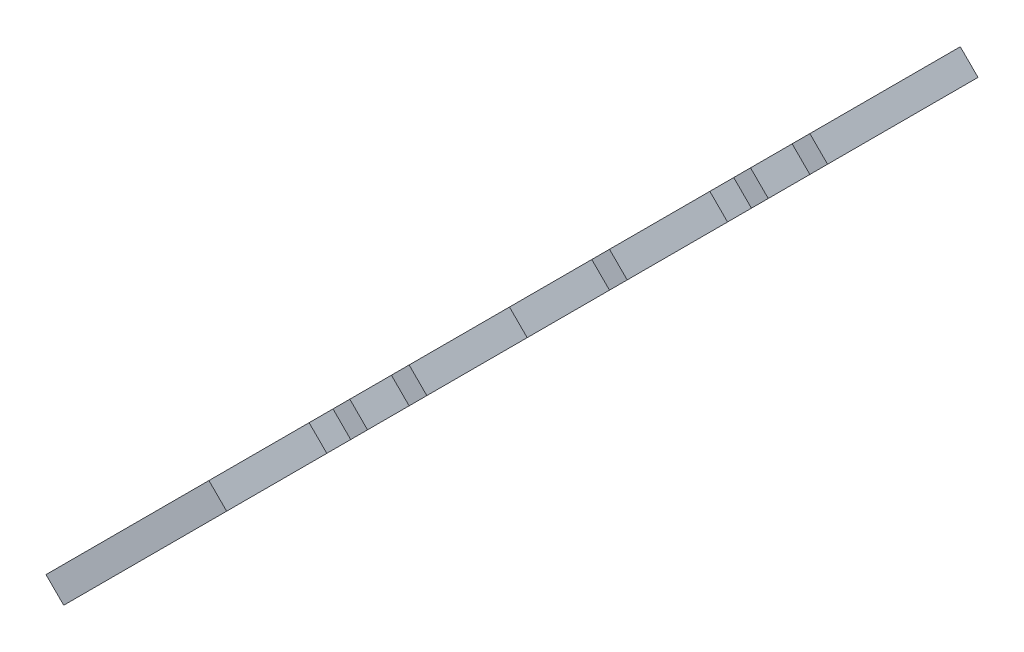
SolidWorks part; units mm, degrees
ref_plane "Front Plane" through (0, 0, 0) normal (0, 0, 1) x (1, 0, 0)
ref_plane "Top Plane" through (0, 0, 0) normal (0, 1, 0) x (1, 0, 0)
ref_plane "Right Plane" through (0, 0, 0) normal (1, 0, 0) x (0, 0, -1)
sketch "Sketch1" plane through (0, 0, 0) normal (0, 0, 1) x (1, 0, 0)
  line L0 (-110.4572, 6.7859) -> (-69.148, 48.095)
  line L1 (-110.4572, 6.7859) -> (-114.9473, 11.276)
  line L2 (-69.148, 48.095) -> (-73.6381, 52.5852)
  line L3 (-114.9473, 11.276) -> (-73.6381, 52.5852)
  line L4 (-74.5361, -29.1352) -> (-70.046, -24.645) construction
extrude "Boss-Extrude1" add sketch "Sketch1" along normal up to surface (190.5 mm away)
sketch "Sketch2" plane through (-63.1116, 63.1116, 0) normal (-0.7071, 0.7071, 0) x (0, 0, 1)
  line L0 (190.5, -14.8867) -> (0, -14.8867) construction
  line L1 (165.1, -21.2367) -> (139.7412, -21.2367)
  line L2 (165.1, -21.2367) -> (165.1, -14.8867)
  line L3 (165.1, -14.8867) -> (139.7412, -14.8867)
  line L4 (139.7412, -21.2367) -> (139.7412, -14.8867)
  line L5 (190.5, -73.3067) -> (0, -73.3067) construction
  line L6 (165.1, -66.9567) -> (139.7412, -66.9567)
  line L7 (165.1, -66.9567) -> (165.1, -73.3067)
  line L8 (165.1, -73.3067) -> (139.7412, -73.3067)
  line L9 (139.7412, -66.9567) -> (139.7412, -73.3067)
  dimension "D1" = 25.3588
extrude "Cut-Extrude1" cut sketch "Sketch2" against normal blind 6.35
pattern_linear "LPattern1" count 3 spacing 50.8 along (0, 0, -1) of "Cut-Extrude1"
sketch "Sketch3" plane through (0, 0, 0) normal (0, 0, -1) x (-1, 0, 0)
  line L0 (94.2927, 22.9503) -> (98.7828, 27.4404)
  line L1 (110.4572, 6.7859) -> (69.148, 48.095) construction
  line L2 (73.6381, 52.5852) -> (114.9473, 11.276) construction
  line L3 (98.7828, 27.4404) -> (89.8026, 36.4207)
  line L4 (89.8026, 36.4207) -> (85.3124, 31.9306)
  line L6 (85.3124, 31.9306) -> (94.2927, 22.9503)
  line L7 (98.7828, 36.4207) -> (83.4753, 21.1131) construction
  line L8 (69.148, 48.095) -> (73.6381, 52.5852) construction
  line L9 (114.9473, 11.276) -> (110.4572, 6.7859) construction
  dimension "D1" = 12.7
  dimension "D2" = 6.35
extrude "Boss-Extrude2" add sketch "Sketch3" along normal blind 6.35
sketch "Sketch5" plane through (-58.6215, 58.6215, 0) normal (0.7071, -0.7071, 0) x (0, 0, -1)
  line L0 (-179.9336, -73.3067) -> (-175.6664, -66.9567) construction
  line L1 (-190.5, -73.3067) -> (-165.1, -73.3067) construction
  line L2 (-179.9336, -66.9567) -> (-179.9336, -73.3067) construction
  line L3 (-175.6664, -73.3067) -> (-179.9336, -66.9567) construction
  line L4 (-175.6664, -66.9567) -> (-175.6664, -73.3067) construction
  line L5 (-78.3336, -73.3067) -> (-74.0664, -66.9567) construction
  line L6 (-88.9412, -73.3067) -> (-63.5, -73.3067) construction
  line L7 (-78.3336, -66.9567) -> (-78.3336, -73.3067) construction
  line L8 (-74.0664, -73.3067) -> (-78.3336, -66.9567) construction
  line L9 (-74.0664, -66.9567) -> (-74.0664, -73.3067) construction
  line L10 (-18.0086, -73.3067) -> (-13.7414, -66.9567) construction
  line L11 (-38.1412, -73.3067) -> (0, -73.3067) construction
  line L12 (-18.0086, -66.9567) -> (-18.0086, -73.3067) construction
  line L13 (-13.7414, -73.3067) -> (-18.0086, -66.9567) construction
  line L14 (-13.7414, -66.9567) -> (-13.7414, -73.3067) construction
  circle A0 centre (-177.8, -70.1317) radius 2.0955
  circle A1 centre (-76.2, -70.1317) radius 2.0955
  circle A2 centre (-15.875, -70.1317) radius 2.0955
  dimension "D1" = 4.191
extrude "Cut-Extrude2" cut sketch "Sketch5" against normal through all
ref_plane "Midplane" through (-31.1811, -31.1811, 0) normal (-0.7071, -0.7071, 0) x (-0.7071, 0.7071, 0)
mirror "Mirror1" about plane through (-31.1811, -31.1811, 0) normal (-0.7071, -0.7071, 0) of "Cut-Extrude2"
sketch "Sketch6" plane through (-63.1116, 63.1116, 0) normal (-0.7071, 0.7071, 0) x (0, 0, 1)
  line L0 (152.4206, -3.6091) -> (152.4206, -40.9822) construction
  line L1 (139.7412, -14.8867) -> (139.7412, -21.2367) construction
  line L2 (165.1, -21.2367) -> (165.1, -14.8867) construction
  line L3 (50.8206, 6.6062) -> (50.8206, -35.0025) construction
  line L4 (38.1412, -14.8867) -> (38.1412, -21.2367) construction
  line L5 (63.5, -21.2367) -> (63.5, -14.8867) construction
  line L7 (38.1412, -21.2367) -> (63.5, -21.2367) construction
  line L11 (139.7412, -21.2367) -> (165.1, -21.2367) construction
  line B0 (52.9542, -21.2367) -> (48.687, -21.2367)
  line B1 (48.687, -33.1747) -> (46.3756, -33.1747)
  line B2 (46.3756, -33.1747) -> (46.3756, -29.9997)
  line B3 (46.3756, -29.9997) -> (48.687, -29.9997)
  line B4 (48.687, -29.9997) -> (48.687, -21.2367)
  line B5 (48.687, -33.1747) -> (48.687, -36.4767)
  line B6 (48.687, -36.4767) -> (52.9542, -36.4767)
  line B7 (52.9542, -33.1747) -> (52.9542, -36.4767)
  line B8 (52.9542, -29.9997) -> (52.9542, -21.2367)
  line B9 (55.2656, -29.9997) -> (52.9542, -29.9997)
  line B10 (55.2656, -33.1747) -> (55.2656, -29.9997)
  line B11 (52.9542, -33.1747) -> (55.2656, -33.1747)
  line B12 (154.5542, -21.2367) -> (150.287, -21.2367)
  line B13 (150.287, -33.1747) -> (147.9756, -33.1747)
  line B14 (147.9756, -33.1747) -> (147.9756, -29.9997)
  line B15 (147.9756, -29.9997) -> (150.287, -29.9997)
  line B16 (150.287, -29.9997) -> (150.287, -21.2367)
  line B17 (150.287, -33.1747) -> (150.287, -36.4767)
  line B18 (150.287, -36.4767) -> (154.5542, -36.4767)
  line B19 (154.5542, -33.1747) -> (154.5542, -36.4767)
  line B20 (154.5542, -29.9997) -> (154.5542, -21.2367)
  line B21 (156.8656, -29.9997) -> (154.5542, -29.9997)
  line B22 (156.8656, -33.1747) -> (156.8656, -29.9997)
  line B23 (154.5542, -33.1747) -> (156.8656, -33.1747)
sketch_block_instance "TSlot-1"
sketch_block "TSlot" parameters "D1"=3.302, "D2"=3.175
sketch_block_instance "TSlot-2"
extrude "Cut-Extrude3" cut sketch "Sketch6" against normal through all
mirror "Mirror2" about plane through (-31.1811, -31.1811, 0) normal (-0.7071, -0.7071, 0) of "Cut-Extrude3"
sketch "Sketch7" plane through (-63.1116, 63.1116, 0) normal (-0.7071, 0.7071, 0) x (0, 0, 1)
  line L0 (0, -26.3167) -> (12.9166, -26.3167) construction
  line L1 (0, -14.8867) -> (0, -37.7467) construction
  line L2 (0, -61.8767) -> (18.0361, -61.8767) construction
  line L3 (0, -50.4467) -> (0, -73.3067) construction
  line B0 (0, -24.1831) -> (0, -28.4503)
  line B1 (11.938, -28.4503) -> (11.938, -30.7617)
  line B2 (11.938, -30.7617) -> (8.763, -30.7617)
  line B3 (8.763, -30.7617) -> (8.763, -28.4503)
  line B4 (8.763, -28.4503) -> (0, -28.4503)
  line B5 (11.938, -28.4503) -> (15.24, -28.4503)
  line B6 (15.24, -28.4503) -> (15.24, -24.1831)
  line B7 (11.938, -24.1831) -> (15.24, -24.1831)
  line B8 (8.763, -24.1831) -> (0, -24.1831)
  line B9 (8.763, -21.8717) -> (8.763, -24.1831)
  line B10 (11.938, -21.8717) -> (8.763, -21.8717)
  line B11 (11.938, -24.1831) -> (11.938, -21.8717)
  line B12 (0, -59.7431) -> (0, -64.0103)
  line B13 (11.938, -64.0103) -> (11.938, -66.3217)
  line B14 (11.938, -66.3217) -> (8.763, -66.3217)
  line B15 (8.763, -66.3217) -> (8.763, -64.0103)
  line B16 (8.763, -64.0103) -> (0, -64.0103)
  line B17 (11.938, -64.0103) -> (15.24, -64.0103)
  line B18 (15.24, -64.0103) -> (15.24, -59.7431)
  line B19 (11.938, -59.7431) -> (15.24, -59.7431)
  line B20 (8.763, -59.7431) -> (0, -59.7431)
  line B21 (8.763, -57.4317) -> (8.763, -59.7431)
  line B22 (11.938, -57.4317) -> (8.763, -57.4317)
  line B23 (11.938, -59.7431) -> (11.938, -57.4317)
sketch_block_instance "TSlot-3"
sketch_block_instance "TSlot-4"
extrude "Cut-Extrude4" cut sketch "Sketch7" against normal through all
